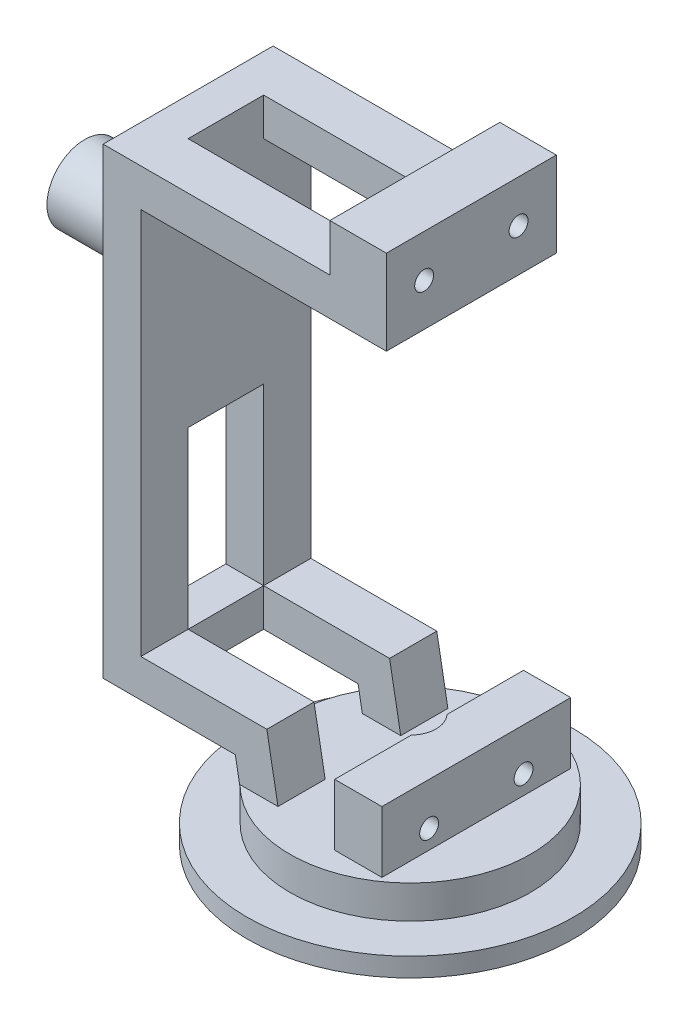
SolidWorks part; units mm, degrees
ref_plane "Front Plane" through (0, 0, 0) normal (0, 0, 1) x (1, 0, 0)
ref_plane "Top Plane" through (0, 0, 0) normal (0, 1, 0) x (1, 0, 0)
ref_plane "Right Plane" through (0, 0, 0) normal (1, 0, 0) x (0, 0, -1)
sketch "Sketch1" plane through (0, 0, 0) normal (0, 1, 0) x (1, 0, 0)
  line L0 (-20, 0) -> (20, 0) construction
  line L1 (-20, -12.5) -> (20, -12.5)
  line L2 (-20, -12.5) -> (-20, 12.5)
  line L3 (-20, 12.5) -> (20, 12.5)
  line L4 (20, -12.5) -> (20, 12.5)
  line L5 (-20, -12.5) -> (20, 12.5) construction
  line L6 (-20, 12.5) -> (20, -12.5) construction
  line L7 (0, 12.5) -> (0, -12.5) construction
  line L8 (-7.9106, 3.9553) -> (7.0894, 3.9553)
  line L9 (-7.9106, 3.9553) -> (-7.9106, -3.5447)
  line L10 (-7.9106, -3.5447) -> (7.0894, -3.5447)
  line L11 (7.0894, 3.9553) -> (7.0894, -3.5447)
  line L12 (-7.9106, 3.9553) -> (7.0894, -3.5447) construction
  line L13 (-7.9106, -3.5447) -> (7.0894, 3.9553) construction
  circle A0 centre (0, 7.9553) radius 1
  circle A1 centre (0, -7.5447) radius 1
  circle A2 centre (16, 0) radius 1
  circle A3 centre (-16, 0) radius 1
  point P0 (0, 0)
  point P8 (0, 0)
  dimension "D5" = 2
  dimension "D7" = 2
  dimension "D9" = 2
  dimension "D1" = 40
  dimension "D2" = 25
  dimension "D3" = 15
  dimension "D4" = 7.5
  dimension "D6" = 4
  dimension "D8" = 4
  dimension "D10" = 16
extrude "Boss-Extrude1" add sketch "Sketch1" along normal blind 2 contours L2 L1 L4 L3
sketch "Sketch2" plane through (0, 2, 0) normal (0, 1, 0) x (1, 0, 0)
  line L1 (2, 10) -> (7, 10)
  line L2 (2, 10) -> (2, -10)
  line L3 (2, -10) -> (7, -10)
  line L4 (7, 10) -> (7, -10)
  line L5 (20, -12.5) -> (20, 12.5) construction
  point P6 (20, 0)
  point P7 (7, 0)
  dimension "D1" = 20
  dimension "D2" = 13
  dimension "D3" = 5
extrude "Boss-Extrude2" add sketch "Sketch2" along normal blind 10
sketch "Sketch4" plane through (7, 0, 0) normal (1, 0, 0) x (0, 0, -1)
  line L0 (-7.046, 10.16) -> (2.954, 10.16) construction
  line L3 (-10, 12) -> (9.965, 12)
  line L4 (-10, 12) -> (-10, 6)
  line L5 (-10, 6) -> (9.965, 6)
  line L6 (9.965, 12) -> (9.965, 6)
  dimension "D1" = 10
  dimension "D2" = 6
extrude "Boss-Extrude3" add sketch "Sketch4" against normal up to surface (5 mm away) up to face at (2, 7, 0)
sketch "Sketch5" plane through (7, 0, 0) normal (1, 0, 0) x (0, 0, -1)
  line L0 (-5, 7.5) -> (5, 7.5) construction
  line L1 (-10, 12) -> (10, 12) construction
  circle A0 centre (5, 7.5) radius 1
  circle A1 centre (-5, 7.5) radius 1
  point P4 (0, 12)
  point P5 (0, 7.5)
  dimension "D2" = 2
  dimension "D3" = 2
  dimension "D1" = 10
  dimension "D4" = 4.5
extrude "Cut-Extrude2" cut sketch "Sketch5" against normal up to surface (5 mm away) up to face at (2, 7, 0)
sketch "Sketch6" plane through (0, 2, 0) normal (0, 1, 0) x (1, 0, 0)
  line L0 (-20, 12.5) -> (-20, -12.5) construction
  line L1 (-13.5277, 9) -> (-9.5277, 9)
  line L2 (-13.5277, 9) -> (-13.5277, -9)
  line L3 (-13.5277, -9) -> (-9.5277, -9)
  line L4 (-9.5277, 9) -> (-9.5277, -9)
  line L10 (-13.5277, 4) -> (-9.5277, 4)
  line L11 (-13.5277, 4) -> (-13.5277, -4)
  line L12 (-13.5277, -4) -> (-9.5277, -4)
  line L13 (-9.5277, 4) -> (-9.5277, -4)
  point P6 (-20, 0)
  point P7 (-13.5277, 0)
  point P12 (-13.5277, 0)
  dimension "D1" = 4
  dimension "D2" = 18
  dimension "D3" = 4
  dimension "D4" = 8
extrude "Boss-Extrude4" add sketch "Sketch6" along normal blind 10 contours L12 L2 L3 L4 | L2 L10 L4 L1 region at (-11.5277, 2, -6.5) region at (-11.5277, 2, 6.5)
sketch "Sketch8" plane through (-13.5277, 0, 0) normal (-1, 0, 0) x (0, 0, 1)
  line L1 (-9, 12) -> (-4, 12)
  line L2 (-9, 12) -> (-9, 8)
  line L3 (-9, 8) -> (-4, 8)
  line L4 (-4, 12) -> (-4, 8)
  dimension "D1" = 5
  dimension "D2" = 4
ref_plane "Plane1" through (0, 0, 0) normal (0, 0, -1) x (-1, 0, 0)
extrude "Boss-Extrude5" add sketch "Sketch8" along normal blind 10
mirror "Mirror1" about plane through (0, 0, 0) normal (0, 0, -1) of "Boss-Extrude5"
sketch "Sketch9" plane through (0, 12, 0) normal (0, 1, 0) x (1, 0, 0)
  line L0 (-23.5277, 4) -> (-9.5277, 4) construction
  line L1 (-23.5277, 9) -> (-19.5277, 9)
  line L2 (-23.5277, 9) -> (-23.5277, 4)
  line L3 (-23.5277, 4) -> (-19.5277, 4)
  line L4 (-19.5277, 9) -> (-19.5277, 4)
  dimension "D1" = 4
  dimension "D2" = 0
extrude "Boss-Extrude6" add sketch "Sketch9" along normal blind 45
mirror "Mirror2" about plane through (0, 0, 0) normal (0, 0, -1) of "Boss-Extrude5"
mirror "Mirror3" about plane through (0, 0, 0) normal (0, 0, -1) of "Boss-Extrude6"
sketch "Sketch12" plane through (-23.5277, 0, 0) normal (-1, 0, 0) x (0, 0, 1)
  line L0 (9, 57) -> (9, 8) construction
  line L1 (-9, 57) -> (9, 57)
  line L2 (-9, 57) -> (-9, 53)
  line L3 (-9, 53) -> (9, 53)
  line L4 (9, 57) -> (9, 53)
  line L5 (-10, 12) -> (10, 12) construction
  line L6 (-9, 8) -> (9, 8)
  line L7 (-9, 8) -> (-9, 12)
  line L8 (-9, 12) -> (9, 12)
  line L9 (9, 8) -> (9, 12)
  line L10 (-9, 32.5) -> (9, 32.5) construction
  line L11 (-9, 57) -> (-9, 8) construction
  line L13 (-9, 30.5) -> (9, 30.5)
  line L14 (-9, 30.5) -> (-9, 34.5)
  line L15 (-9, 34.5) -> (9, 34.5)
  line L16 (9, 30.5) -> (9, 34.5)
  line L17 (-9, 30.5) -> (9, 34.5) construction
  line L18 (-9, 34.5) -> (9, 30.5) construction
  point P18 (0, 32.5)
  dimension "D1" = 4
  dimension "D2" = 4
  dimension "D3" = 4
extrude "Boss-Extrude8" add sketch "Sketch12" against normal up to surface (4 mm away) up to face at (-19.5277, 34.5, 6.5)
sketch "Sketch13" plane through (-19.5277, 0, 0) normal (1, 0, 0) x (0, 0, -1)
  line L1 (-9, 57) -> (-4, 57)
  line L2 (-9, 57) -> (-9, 53)
  line L3 (-9, 53) -> (-4, 53)
  line L4 (-4, 57) -> (-4, 53)
  line L5 (9, 57) -> (4, 57)
  line L6 (9, 57) -> (9, 53)
  line L7 (9, 53) -> (4, 53)
  line L8 (4, 57) -> (4, 53)
extrude "Boss-Extrude9" add sketch "Sketch13" along normal blind 26
sketch "Sketch14" plane through (6.4723, 0, 0) normal (1, 0, 0) x (0, 0, -1)
  line L0 (-9, 57) -> (9, 57)
  line L1 (-9, 57) -> (-9, 53)
  line L2 (9, 57) -> (9, 53)
  line L3 (-9, 53) -> (9, 53)
  line L4 (-9, 53) -> (-4, 53) construction
extrude "Boss-Extrude10" add sketch "Sketch14" against normal blind 6
sketch "Sketch15" plane through (6.4723, 0, 0) normal (1, 0, 0) x (0, 0, -1)
  line L0 (-5, 57.5) -> (5, 57.5) construction
  line L1 (-9, 53) -> (9, 53) construction
  line L2 (-5, 7.5) -> (-5, 57.5) construction
  circle A0 centre (-5, 57.5) radius 1
  circle A1 centre (5, 57.5) radius 1
  dimension "D3" = 2
  dimension "D4" = 2
  dimension "D1" = 10
  dimension "D2" = 4.5
sketch "Sketch16" plane through (0, 57, 0) normal (0, 1, 0) x (1, 0, 0)
  line L0 (6.4723, 9) -> (6.4723, -9)
  line L1 (6.4723, 9) -> (0.4841, 9)
  line L2 (6.4723, -9) -> (0.4841, -9)
  line L3 (0.4841, 9) -> (0.4841, -9)
extrude "Boss-Extrude11" add sketch "Sketch16" along normal blind 5
extrude "Cut-Extrude3" cut sketch "Sketch15" against normal blind 6
sketch "Sketch17" plane through (0, 0, 0) normal (0, -1, 0) x (1, 0, 0)
  circle A0 centre (0, 0) radius 3
  circle A1 centre (0, 0) radius 5
  dimension "D1" = 6
  dimension "D2" = 2
sketch "Sketch18" plane through (-23.5277, 0, 0) normal (-1, 0, 0) x (0, 0, 1)
  line L0 (0, 0) -> (0, 62) construction
  line L1 (-9, 62) -> (9, 62) construction
  line L2 (-17.0412, 42) -> (24.329, 42) construction
  line L3 (12.5, 0) -> (-12.5, 0) construction
  dimension "42" = 42
extrude "Cut-Extrude5" cut sketch "Sketch17" against normal blind 6 contours A0
ref_plane "Plane2" through (0, 1, 0) normal (0, -1, 0) x (-1, 0, 0)
ref_plane "Plane3" through (0, 3, 0) normal (0, 1, 0) x (1, 0, 0)
sketch "Sketch20" plane through (0, 3, 0) normal (0, 1, 0) x (1, 0, 0)
  circle A0 centre (0, 0) radius 3
  circle A1 centre (0, 0) radius 5
  dimension "D1" = 6
  dimension "D2" = 2
sketch "Sketch23" plane through (20, 0, 0) normal (1, 0, 0) x (0, 0, -1)
  line L0 (-12.5, 2) -> (-10.5, 2)
  line L1 (-12.5, 2) -> (-12.5, 59.5)
  line L2 (12.5, 2) -> (12.5, 59.5)
  line L3 (-10.5, 2) -> (-10.5, 59.5)
  line L4 (-12.5, 2) -> (12.5, 2) construction
  line L5 (10.5, 2) -> (10.5, 59.5)
  line L6 (10.5, 2) -> (12.5, 2)
  arc A0 (12.5, 59.5) -> (-12.5, 59.5) centre (0, 59.5) ccw
  arc A1 (10.5, 59.5) -> (-10.5, 59.5) centre (0, 59.5) ccw
  dimension "D2" = 2
sketch "Sketch24" plane through (-23.5277, 0, 0) normal (-1, 0, 0) x (0, 0, 1)
  line L2 (4, 34.5) -> (4, 53) construction
  line L3 (-4, 34.5) -> (4, 34.5)
  line L4 (-4, 34.5) -> (-4, 53)
  line L5 (-4, 53) -> (4, 53)
  line L6 (4, 34.5) -> (4, 53)
  line L7 (-4, 34.5) -> (4, 53) construction
  line L8 (-4, 53) -> (4, 34.5) construction
  line L9 (4, 34.5) -> (-4, 34.5) construction
  line M1 (4, 53) -> (4, 34.5)
  line M3 (-4, 34.5) -> (-4, 53)
extrude "Boss-Extrude18" add sketch "Sketch24" against normal blind 4 contours L5 L3 M3 | L3 L5 M1 region at (-23.5277, 43.75, 0)
extrude "Boss-Extrude20" add sketch "Sketch20" against normal blind 1
sketch "Sketch26" plane through (0, 3, 0) normal (0, 1, 0) x (1, 0, 0)
  circle A0 centre (0, 0) radius 2.9983
  circle A1 centre (0, 0) radius 5
  circle A2 centre (0, 0) radius 1.5
  line M1 (2, -4.5826) -> (2, -2.2361)
  arc M2 (2, -2.2361) -> (2, 2.2361) centre (0, 0) cw
  line M3 (2, 2.2361) -> (2, 4.5826)
  arc M4 (2, 4.5826) -> (2, -4.5826) centre (0, 0) ccw
  dimension "D1" = 3
extrude "Boss-Extrude21" add sketch "Sketch26" along normal blind 1 contours A0 A2 | M4 M1 M2 M3 region at (-2.9135, 3, 0) region at (1.8779, 3, -3.4093)
sketch "Sketch27" plane through (0, 4, 0) normal (0, 1, 0) x (1, 0, 0)
  circle A0 centre (0, 0) radius 5
  circle A1 centre (0, 0) radius 2.75
  dimension "D1" = 5.5
extrude "Boss-Extrude22" add sketch "Sketch27" along normal blind 2
sketch "Sketch28" plane through (0, 6, 0) normal (0, 1, 0) x (1, 0, 0)
  circle A0 centre (0, 0) radius 2.75
extrude "Cut-Extrude10" cut sketch "Sketch28" along normal blind 10
sketch "Sketch30" plane through (-23.5277, 0, 0) normal (-1, 0, 0) x (0, 0, 1)
  line L0 (-9, 32.5) -> (9, 32.5) construction
  line L1 (-9, 57) -> (-9, 8) construction
  line L2 (9, 57) -> (9, 8) construction
  line L3 (0, 57) -> (0, 8) construction
  line L4 (-9, 57) -> (9, 57) construction
  line L5 (-9, 8) -> (9, 8) construction
sketch "Sketch31" plane through (-23.5277, 0, 0) normal (-1, 0, 0) x (0, 0, 1)
  circle A0 centre (-0.05, 43.4) radius 4
  dimension "D1" = 8
extrude "Boss-Extrude23" add sketch "Sketch31" along normal blind 11
sketch "Sketch32" plane through (0, 0, 0) normal (0, -1, 0) x (1, 0, 0)
  circle A0 centre (0, 0) radius 23.585
extrude "Boss-Extrude24" add sketch "Sketch32" against normal blind 2
sketch "Sketch33" plane through (0, 0, 0) normal (0, -1, 0) x (1, 0, 0)
  circle A0 centre (0, 0) radius 3
  dimension "D1" = 6
extrude "Cut-Extrude11" cut sketch "Sketch33" against normal blind 3
sketch "Sketch34" plane through (0, 2, 0) normal (0, 1, 0) x (1, 0, 0)
  line L2 (-10.2128, 21.7186) -> (-10.2128, 13.9525)
  line L3 (-10.2128, 13.9525) -> (10.2128, 13.9525)
  line L4 (10.2128, 21.7186) -> (10.2128, 13.9525)
  arc A0 (10.2128, 21.7186) -> (-10.2128, 21.7186) centre (0, 0) ccw
  point P7 (0, 13.9525)
  dimension "D3" = 48
extrude "Cut-Extrude12" cut sketch "Sketch34" against normal blind 10
sketch "Sketch35" plane through (0, 0, 0) normal (0, -1, 0) x (1, 0, 0)
  line L0 (-17.2908, 0) -> (-23.585, 0)
  line L1 (-10.2128, -13.9525) -> (-10.2128, -21.2591)
  arc A0 (-23.585, 0) -> (-10.2128, -21.2591) centre (0, 0) ccw
  arc A1 (-17.2908, 0) -> (-10.2128, -13.9525) centre (0, 0) ccw
extrude "Cut-Extrude13" cut sketch "Sketch35" against normal blind 4
sketch "Sketch36" plane through (0, 0, 0) normal (0, -1, 0) x (1, 0, 0)
  line L0 (-10.2128, -13.9525) -> (10.2128, -13.9525)
  arc A0 (-10.2128, -13.9525) -> (10.2128, -13.9525) centre (0, 0) ccw
extrude "Boss-Extrude25" add sketch "Sketch36" against normal blind 2
sketch "Sketch37" plane through (0, 0, 0) normal (0, -1, 0) x (1, 0, 0)
  line L3 (-23.585, 0) -> (-17.2908, 0)
  line L4 (10.2128, -21.2591) -> (10.2128, -13.9525)
  arc A6 (10.2128, -13.9525) -> (-17.2908, 0) centre (0, 0) ccw
  arc A7 (10.2128, -21.2591) -> (-23.585, 0) centre (0, 0) ccw
extrude "Cut-Extrude15" cut sketch "Sketch37" against normal up to surface (2 mm away) up to face at (-1.3725, 2, -3.2655)
sketch "Sketch38" plane through (0, 0, 9) normal (0, 0, 1) x (1, 0, 0)
  line L1 (-9.5277, 2) -> (-13.5277, 2)
  line L2 (-9.5277, 2) -> (-9.5277, 8)
  line L3 (-9.5277, 8) -> (-13.5277, 8)
  line L4 (-13.5277, 2) -> (-13.5277, 8)
extrude "Cut-Extrude16" cut sketch "Sketch38" against normal through all
sketch "Sketch39" plane through (0, 0, 9) normal (0, 0, 1) x (1, 0, 0)
  line L0 (-9.5277, 8) -> (-8.44, 2)
  line L1 (17.2908, 2) -> (-17.2908, 2) construction
  line L2 (-9.5277, 12) -> (-6.1876, 12)
  line L3 (-6.1876, 12) -> (-4.3748, 2)
  line L4 (-9.5277, 12) -> (-9.5277, 8)
  line L5 (-8.44, 2) -> (-4.3748, 2)
  dimension "D1" = 4
extrude "Boss-Extrude26" add sketch "Sketch39" against normal blind 5
mirror "Mirror4" about plane through (0, 0, 0) normal (0, 0, -1) of "Boss-Extrude26"
sketch "Sketch40" plane through (0, 0, 0) normal (0, -1, 0) x (1, 0, 0)
  circle A0 centre (0, 0) radius 10.75
  dimension "D1" = 21.5
extrude "Cut-Extrude17" cut sketch "Sketch40" against normal blind 3.5
sketch "Sketch41" plane through (0, 2, 0) normal (0, 1, 0) x (1, 0, 0)
  circle A0 centre (0, 0) radius 10.75
  circle A1 centre (0, 0) radius 12.75
  dimension "D1" = 21.5
  dimension "D2" = 2
extrude "Boss-Extrude27" add sketch "Sketch41" along normal blind 1.5
sketch "Sketch42" plane through (0, 3.5, 0) normal (0, 1, 0) x (1, 0, 0)
  circle A0 centre (0, 0) radius 12.75
extrude "Boss-Extrude28" add sketch "Sketch42" along normal blind 2
sketch "Sketch43" plane through (0, 5.5, 0) normal (0, 1, 0) x (1, 0, 0)
  circle A0 centre (0, 0) radius 3
  dimension "D1" = 6
extrude "Cut-Extrude18" cut sketch "Sketch43" against normal blind 2
sketch "Sketch44" plane through (0, 6, 0) normal (0, 1, 0) x (1, 0, 0)
  circle A0 centre (0, 0) radius 5
extrude "Cut-Extrude19" cut sketch "Sketch44" against normal up to surface (0.5 mm away) up to face at (2.5, 5.5, 0)
sketch "Sketch45" plane through (0, 5.5, 0) normal (0, 1, 0) x (1, 0, 0)
  line L0 (2, 2.2361) -> (2, 10)
  line L1 (2, -10) -> (7, -10)
  line L2 (2, -10) -> (2, -2.2361)
  line L3 (2, 10) -> (7, 10)
  line L4 (7, -10) -> (7, 10)
  arc A0 (2, -2.2361) -> (2, 2.2361) centre (0, 0) ccw
extrude "Boss-Extrude29" add sketch "Sketch45" along normal blind 1
equation "\"inner-diameter\"= 10mm"
equation "\"outer-diameter\"= 20mm"
